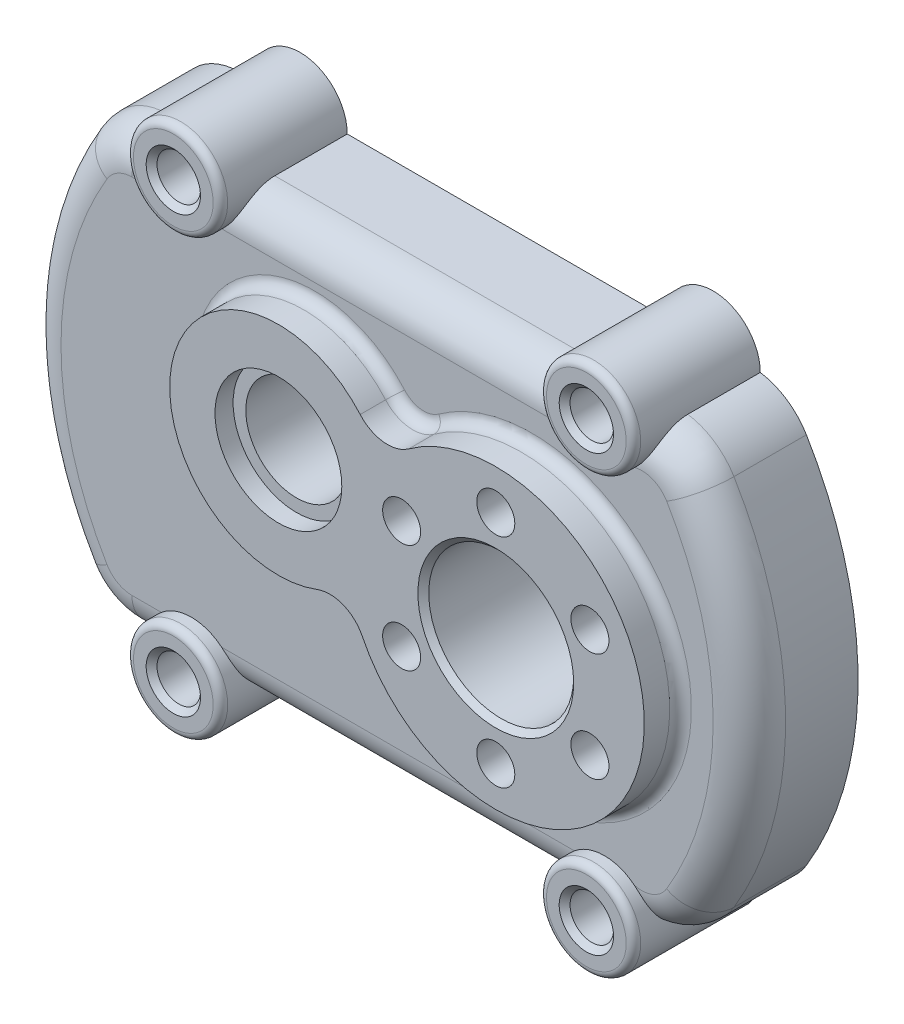
SolidWorks part; units mm, degrees
ref_plane "Front Plane" through (0, 0, 0) normal (0, 0, 1) x (1, 0, 0)
ref_plane "Top Plane" through (0, 0, 0) normal (0, 1, 0) x (1, 0, 0)
ref_plane "Right Plane" through (0, 0, 0) normal (1, 0, 0) x (0, 0, -1)
sketch "Sketch1" plane through (0, 0, 0) normal (0, 0, 1) x (1, 0, 0)
  line L1 (80, -60) -> (-80, -60)
  line L3 (80, 60) -> (-80, 60)
  line L5 (80, -60) -> (-80, 60) construction
  line L6 (80, 60) -> (-80, -60) construction
  arc A0 (-80, 60) -> (-80, -60) centre (0, 0) ccw
  arc A1 (80, -60) -> (80, 60) centre (0, 0) ccw
  point P7 (0, 0)
  dimension "D1" = 200
  dimension "D2" = 120
extrude "Boss-Extrude1" add sketch "Sketch1" along normal blind 30
sketch "Sketch2" plane through (0, 0, 30) normal (0, 0, 1) x (1, 0, 0)
  arc A0 (3.1668, -18.0087) -> (15.9748, 33.2233) centre (40, 0) ccw
  arc A1 (80, -60) -> (80, 60) centre (0, 0) ccw construction
  arc A2 (2.5862, 34.7449) -> (-9.3627, -13.0508) centre (-20, 15) ccw
  arc A3 (3.1668, -18.0087) -> (-9.3627, -13.0508) centre (-5.8169, -22.4011) ccw
  arc A4 (15.9748, 33.2233) -> (2.5862, 34.7449) centre (10.115, 41.3266) cw
  dimension "D1" = 82
  dimension "D3" = 60
  dimension "D6" = 10
  dimension "D2" = 60
  dimension "D4" = 60
  dimension "D5" = 15
extrude "Boss-Extrude2" add sketch "Sketch2" along normal blind 10
sketch "Sketch3" plane through (0, 0, 0) normal (0, 0, 1) x (1, 0, 0)
  line L0 (-80, -60) -> (80, -60) construction
  line L1 (0, 0) -> (-100, 0) construction
  circle A0 centre (-54, -60) radius 13
  circle A1 centre (60, -60) radius 13
  arc A16 (80, -60) -> (80, 60) centre (0, 0) ccw construction
  arc A17 (-80, 60) -> (-80, -60) centre (0, 0) ccw construction
  circle A18 centre (60, 60) radius 13
  circle A19 centre (-54, 60) radius 13
  dimension "D1" = 26
  dimension "D3" = 40
  dimension "D2" = 114
extrude "Boss-Extrude3" add sketch "Sketch3" along normal blind 35
sketch "Sketch6" plane through (0, 0, 40) normal (0, 0, 1) x (1, 0, 0)
  circle A0 centre (40, 0) radius 20
  circle A2 centre (-20, 15) radius 14
  dimension "D1" = 40
  dimension "D2" = 28
extrude "Cut-Extrude1" cut sketch "Sketch6" against normal up to surface (40 mm away) up to face at (2, 0, 0)
chamfer "Chamfer1" distance 1.5 angle 45 1 edges at (60, 0, 40)
sketch "Sketch7" plane through (0, 0, 40) normal (0, 0, 1) x (1, 0, 0)
  circle A0 centre (-20, 15) radius 17.5
  dimension "D1" = 35
extrude "Cut-Extrude2" cut sketch "Sketch7" against normal blind 5
hole_wizard "Ø12.0 (12) Diameter Hole1" positions "Sketch8" profile "Sketch9" hole size "Ø12.0" standard "ANSI Metric" end condition through all
sketch "Sketch8" plane through (0, 0, 35) normal (0, 0, 1) x (1, 0, 0)
  point P0 (-54, 60)
  point P3 (-54, -60)
  point P6 (60, -60)
  point P9 (60, 60)
sketch "Sketch9" plane through (-54, 60, 35) normal (1, 0, 0) x (0, -1, 0)
  line L0 (0, 0) -> (0, 35)
  line L1 (0, 35) -> (6, 35)
  line L2 (6, 35) -> (6, 0)
  line L5 (6, 0) -> (0, 0)
  line L11 (0, -6.35) -> (0, 107.95) construction
  dimension "Thru Hole Dia." = 12
  dimension "Thru Hole Depth" = 35
chamfer "Chamfer2" distance 1.5 angle 45 4 edges at (-48, 60, 35) (66, 60, 35) (66, -60, 35) (-48, -60, 35)
fillet "Fillet1" radius 2 4 edges at (47, 60, 35) (73, -60, 35) (-41, -60, 35) (-67, 60, 35)
fillet "Fillet2" radius 18 4 edges at (-80, 60, 15) (80, 60, 15) (80, -60, 15) (-80, -60, 15)
fillet "Fillet6" radius 10 9 edges at (3, 60, 30) (80.3235, 57.1576, 30) (100, 0, 30) (80.3235, -57.1576, 30) (3, -60, 30) (-68.7136, -60, 30) (-100, 0, 30) (-68.7136, 60, 30) (-79.3168, 57.6517, 30) tangent propagation no
fillet "Fillet7" radius 3 4 edges at (8.9857, 31.3905, 30) (79.7758, -9.944, 30) (-2.1375, -13.1026, 30) (-49.1043, 22.2761, 30)
hole_wizard "M12x1.5 Tapped Hole1" positions "Sketch10" profile "Sketch11" tap size "M12x1.5" standard "ANSI Metric"
sketch "Sketch10" plane through (0, 0, 40) normal (0, 0, 1) x (1, 0, 0)
  circle A0 centre (40, 0) radius 30 construction
  point P5 (40, 30)
  point P17 (65.9808, 15)
  point P18 (65.9808, -15)
  point P19 (40, -30)
  point P20 (14.0192, -15)
  point P21 (14.0192, 15)
  point P22 (40, 0)
  dimension "D1" = 60
  dimension "D2" = 6
sketch "Sketch11" plane through (40, 0, 40) normal (1, 0, 0) x (0, -1, 0)
  line L0 (0, 0) -> (0, 18.1545)
  line L1 (0, 18.1545) -> (5.25, 15)
  line L2 (5.25, 15) -> (5.25, 0)
  line L5 (5.25, 0) -> (0, 0)
  line L10 (0, 18.1545) -> (-5.25, 15) construction
  line L11 (0, -6.35) -> (0, 107.95) construction
  dimension "Tap Drill Dia." = 10.5
  dimension "Tap Drill Depth" = 15
  dimension "Drill Angle" = 118
cosmetic thread "Hole Thread1" parameters "D1"=24, "D2"=12
cosmetic thread "Hole Thread2" parameters "D1"=24, "D2"=12
cosmetic thread "Hole Thread3" parameters "D1"=24, "D2"=12
cosmetic thread "Hole Thread4" parameters "D1"=24, "D2"=12
cosmetic thread "Hole Thread5" parameters "D1"=24, "D2"=12
cosmetic thread "Hole Thread6" parameters "D1"=24, "D2"=12
